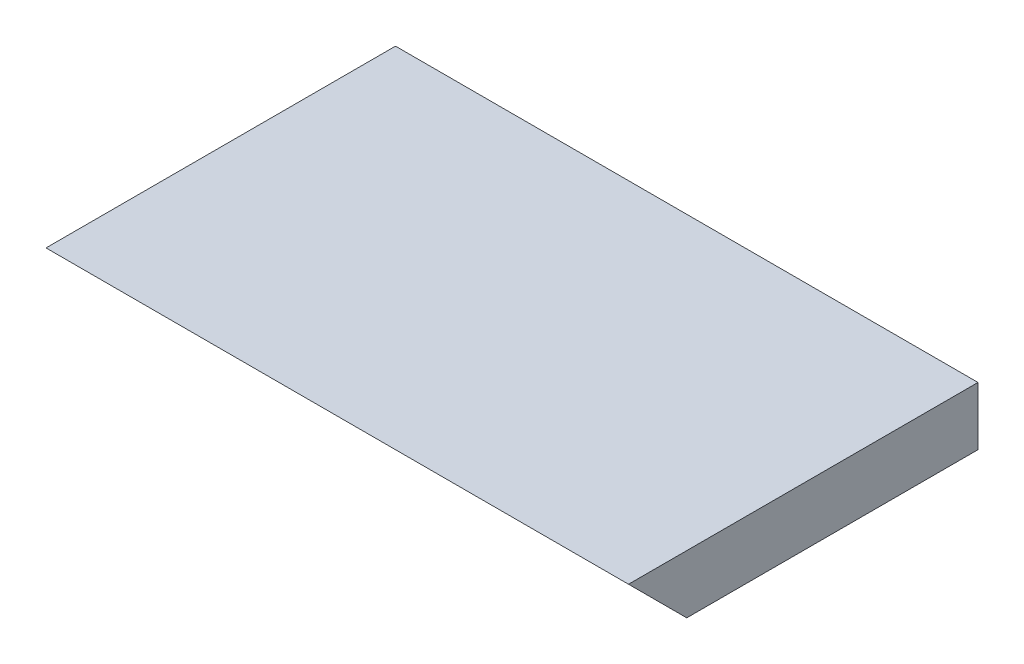
SolidWorks part; units mm, degrees
ref_plane "Front Plane" through (0, 0, 0) normal (0, 0, 1) x (1, 0, 0)
ref_plane "Top Plane" through (0, 0, 0) normal (0, 1, 0) x (1, 0, 0)
ref_plane "Right Plane" through (0, 0, 0) normal (1, 0, 0) x (0, 0, -1)
sketch "Sketch1" plane through (0, 0, 0) normal (0, 1, 0) x (1, 0, 0)
  line L1 (-25, -15) -> (25, -15)
  line L2 (-25, -15) -> (-25, 15)
  line L3 (-25, 15) -> (25, 15)
  line L4 (25, -15) -> (25, 15)
  line L5 (-25, -15) -> (25, 15) construction
  line L6 (-25, 15) -> (25, -15) construction
  point P0 (0, 0)
  dimension "D1" = 50
  dimension "D2" = 30
extrude "Boss-Extrude1" add sketch "Sketch1" along normal blind 5
chamfer "Chamfer1" distance 5 angle 45 1 edges at (0, 0, 15)
